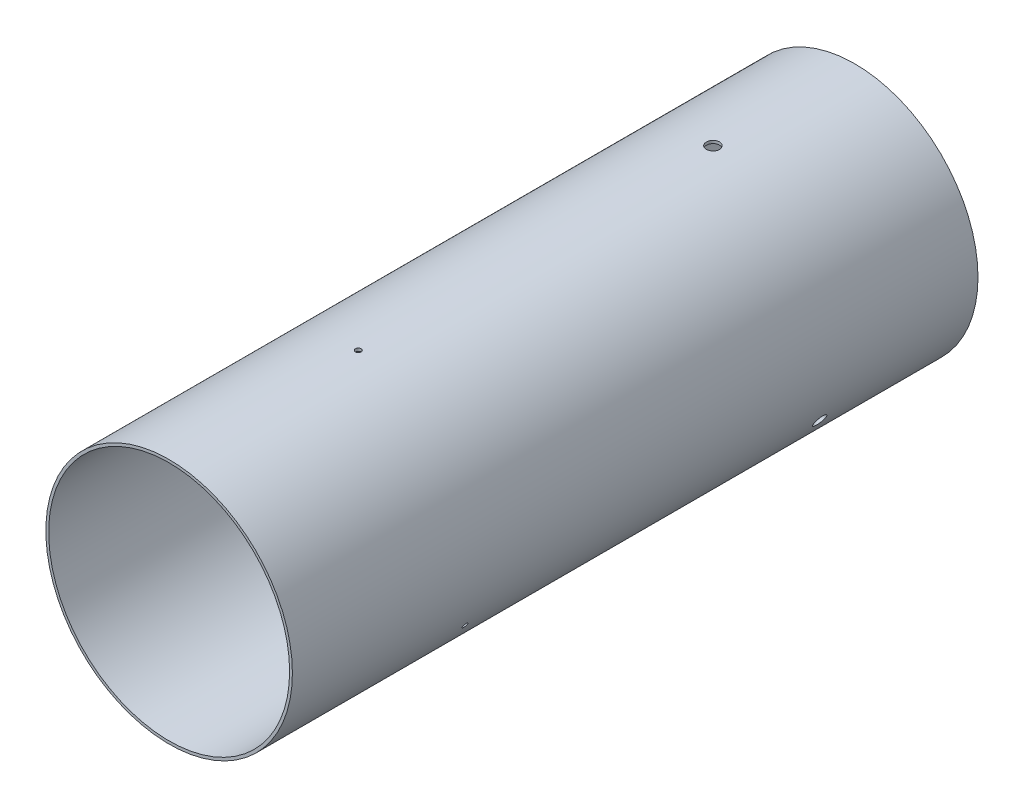
SolidWorks part; units mm, degrees
material "E-Glass Fiber"
ref_plane "Front Plane" through (0, 0, 0) normal (0, 0, 1) x (1, 0, 0)
ref_plane "Top Plane" through (0, 0, 0) normal (0, 1, 0) x (1, 0, 0)
ref_plane "Right Plane" through (0, 0, 0) normal (1, 0, 0) x (0, 0, -1)
sketch "Sketch1" plane through (0, 0, 0) normal (0, 0, 1) x (1, 0, 0)
  circle A0 centre (0, 0) radius 49.6697
  circle A1 centre (0, 0) radius 48.5394
  dimension "D1" = 99.3394
  dimension "D2" = 97.0788
extrude "Boss-Extrude1" add sketch "Sketch1" along normal blind 276.225
ref_plane "Plane1" through (0, 49.6697, 0) normal (0, 1, 0) x (1, 0, 0)
sketch "Sketch2" plane through (0, 49.6697, 0) normal (0, 1, 0) x (1, 0, 0)
  line L0 (0, 0) -> (0, -57.15) construction
  line L1 (0, -57.15) -> (0, 0) construction
  line L2 (-49.6697, -276.225) -> (49.6697, -276.225) construction
  line L3 (0, -57.15) -> (0, -200.025) construction
  line L4 (-48.5394, -276.225) -> (48.5394, -276.225) construction
  circle A0 centre (0, -57.15) radius 2.6289
  circle A2 centre (0, -200.025) radius 1.143
  dimension "D2" = 5.2578
  dimension "D6" = 2.286
  dimension "D1" = 57.15
  dimension "D3" = 276.225
  dimension "D5" = 76.2
extrude "8-32 T-Nut Holes" cut sketch "Sketch2" against normal blind 5.08
sketch "Sketch4" plane through (0, 0, 0) normal (0, 0, -1) x (-1, 0, 0)
  line L0 (0, 49.6697) -> (0, 0) construction
  line L1 (0, 0) -> (43.0152, -24.8348) construction
  circle A0 centre (0, 0) radius 49.6697 construction
  dimension "D1" = 120
ref_plane "Plane2" through (-43.0152, -24.8348, 0) normal (-0.866, -0.5, 0) x (0, 0, 1)
sketch "Sketch3" plane through (-43.0152, -24.8348, 0) normal (-0.866, -0.5, 0) x (0, 0, 1)
  line L0 (0, 0) -> (60.325, 0) construction
  line L1 (60.325, 0) -> (196.85, 0) construction
  line L4 (276.225, -49.6697) -> (276.225, 49.6697) construction
  circle A0 centre (60.325, 0) radius 2.6289
  circle A1 centre (196.85, 0) radius 1.143
  dimension "D3" = 5.2578
  dimension "D4" = 2.286
  dimension "D1" = 60.325
  dimension "D2" = 79.375
extrude "Odd_T-Nut" [suppressed] cut sketch "Sketch3" against normal blind 2.54
pattern_circular "CirPattern1" count 3 over 360 about axis through (0, 0, 276.225) along (0, 0, -1) of "8-32 T-Nut Holes"
